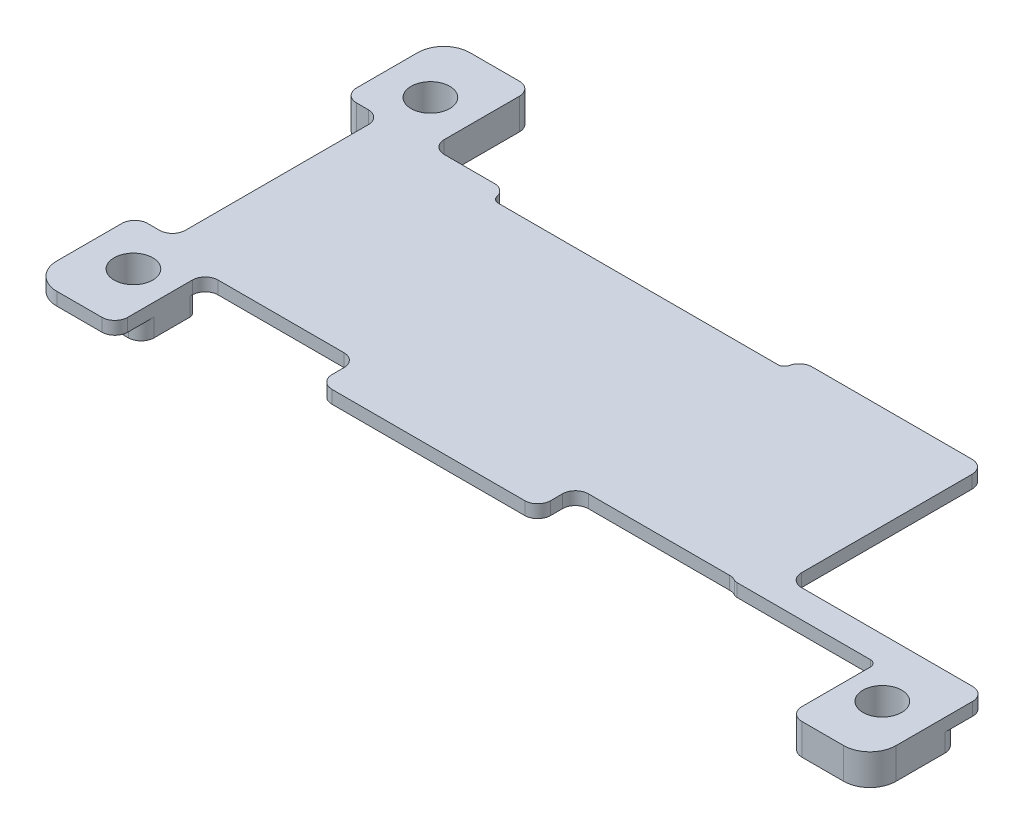
SolidWorks part; units mm, degrees
ref_plane "Front Plane" through (0, 0, 0) normal (0, 0, 1) x (1, 0, 0)
ref_plane "Top Plane" through (0, 0, 0) normal (0, 1, 0) x (1, 0, 0)
ref_plane "Right Plane" through (0, 0, 0) normal (1, 0, 0) x (0, 0, -1)
sketch "Sketch2" plane through (0, 0, 0) normal (0, 1, 0) x (1, 0, 0)
  line L4 (-32.5001, 13.9696) -> (-32.5001, -13.9696)
  line L5 (-30.4681, -16.0016) -> (30.4681, -16.0016)
  line L6 (32.5001, -13.9696) -> (32.5001, 13.9696)
  line L7 (30.4681, 16.0016) -> (-30.4681, 16.0016)
  line L8 (-32.5001, 13.9696) -> (-32.5001, -13.9696)
  line L9 (-30.4681, -16.0016) -> (30.4681, -16.0016)
  line L10 (32.5001, -13.9696) -> (32.5001, 13.9696)
  line L11 (30.4681, 16.0016) -> (-30.4681, 16.0016)
  circle A0 centre (28.9999, 11.4637) radius 1.5 construction
  circle A1 centre (28.9999, -11.5363) radius 1.5 construction
  circle A2 centre (-29.0002, -11.5363) radius 1.5 construction
  circle A3 centre (-29.0002, 11.4637) radius 1.5 construction
  arc A4 (-30.4681, 16.0016) -> (-32.5001, 13.9696) centre (-30.4681, 13.9696) ccw
  arc A5 (-32.5001, -13.9696) -> (-30.4681, -16.0016) centre (-30.4681, -13.9696) ccw
  arc A6 (30.4681, -16.0016) -> (32.5001, -13.9696) centre (30.4681, -13.9696) ccw
  arc A7 (32.5001, 13.9696) -> (30.4681, 16.0016) centre (30.4681, 13.9696) ccw
  arc A8 (-30.4681, 16.0016) -> (-32.5001, 13.9696) centre (-30.4681, 13.9696) ccw
  arc A9 (-32.5001, -13.9696) -> (-30.4681, -16.0016) centre (-30.4681, -13.9696) ccw
  arc A10 (30.4681, -16.0016) -> (32.5001, -13.9696) centre (30.4681, -13.9696) ccw
  arc A11 (32.5001, 13.9696) -> (30.4681, 16.0016) centre (30.4681, 13.9696) ccw
  circle A12 centre (28.9999, 11.4637) radius 1.5
  circle A13 centre (28.9999, -11.5363) radius 1.5
  circle A14 centre (-29.0002, -11.5363) radius 1.5
  circle A15 centre (-29.0002, 11.4637) radius 1.5
  dimension "D1" = 0
extrude "Boss-Extrude1" add sketch "Sketch2" along normal blind 1 from offset 1.4
sketch "Sketch4" plane through (0, 2.4, 0) normal (0, 1, 0) x (1, 0, 0)
  line L0 (30.4681, 16.0016) -> (-30.4681, 16.0016) construction
  line L1 (-25.6391, 16.0016) -> (25.6609, 16.0016)
  line L2 (-25.6391, 16.0016) -> (-25.6391, 8.1735)
  line L3 (-25.6391, 8.1735) -> (25.6609, 8.1735)
  line L4 (25.6609, 16.0016) -> (25.6609, 8.1735)
  line L5 (-25.3891, 13.7969) -> (-25.3891, 9.7969) construction
  line L7 (25.4109, 9.7969) -> (25.4109, 9.9469) construction
  line L8 (16.247, 7.1735) -> (3.847, 7.1735) construction
  dimension "D2" = 0.25
  dimension "D3" = 0.25
  dimension "D1" = 1
extrude "Cut-Extrude1" cut sketch "Sketch4" against normal through all
sketch "Sketch5" plane through (0, 2.4, 0) normal (0, 1, 0) x (1, 0, 0)
  line L1 (17.247, -7.0388) -> (32.5001, -7.0388)
  line L2 (17.247, -7.0388) -> (17.247, 16.0016)
  line L3 (17.247, 16.0016) -> (32.5001, 16.0016)
  line L4 (32.5001, -7.0388) -> (32.5001, 16.0016)
  line L6 (32.5001, 13.9696) -> (32.5001, -13.9696) construction
  line L7 (-30.4681, 16.0016) -> (30.4681, 16.0016) construction
  line L8 (16.247, -7.8265) -> (16.247, 7.1735) construction
  line L9 (29.9856, -6.8888) -> (19.7756, -6.8888) construction
  dimension "D1" = 1
  dimension "D2" = 0.15
extrude "Cut-Extrude2" cut sketch "Sketch5" against normal through all
sketch "Sketch6" plane through (0, 2.4, 0) normal (0, 1, 0) x (1, 0, 0)
  line L0 (-30.4681, -16.0016) -> (30.4681, -16.0016) construction
  line L1 (4.1693, -9.2016) -> (26.2388, -9.2016)
  line L2 (4.1693, -9.2016) -> (4.1693, -16.0016)
  line L3 (4.1693, -16.0016) -> (26.2388, -16.0016)
  line L4 (26.2388, -9.2016) -> (26.2388, -16.0016)
  line L5 (4.4193, -17.3016) -> (4.4193, -9.5016) construction
  line L6 (25.9888, -9.5016) -> (25.9888, -17.0016) construction
  line L7 (5.6693, -9.5016) -> (4.4193, -9.5016) construction
  line L8 (-14.475, -9.6016) -> (-14.475, -17.4016) construction
  line L9 (-25.975, -9.0016) -> (-14.225, -9.0016)
  line L10 (-25.975, -9.0016) -> (-25.975, -16.0016)
  line L11 (-25.975, -16.0016) -> (-14.225, -16.0016)
  line L12 (-14.225, -9.0016) -> (-14.225, -16.0016)
  line L13 (-25.725, -17.4016) -> (-25.725, -9.6016) construction
  line L15 (-10.0891, -9.0016) -> (-26.0891, -9.0016) construction
  dimension "D2" = 0.25
  dimension "D1" = 0.25
  dimension "D4" = 0.25
  dimension "D5" = 0.25
extrude "Cut-Extrude3" cut sketch "Sketch6" against normal through all
sketch "Sketch7" plane through (0, 2.4, 0) normal (0, 1, 0) x (1, 0, 0)
  line L0 (-30.4681, -16.0016) -> (-25.975, -16.0016) construction
  line L2 (2.6974, -11.9253) -> (2.6974, -9.0016)
  line L4 (15.247, -16.0016) -> (15.247, -9.0016)
  line L5 (16.247, -7.8265) -> (16.247, 7.1735) construction
  line L7 (1.6974, -10.9253) -> (1.6974, 4.0747) construction
  line L8 (-13.3026, -10.9253) -> (1.6974, -10.9253) construction
  line L9 (-14.225, -16.0016) -> (15.247, -16.0016)
  line L10 (-14.225, -16.0016) -> (-14.225, -11.9253)
  line L11 (-14.225, -11.9253) -> (2.6974, -11.9253)
  line L13 (-32.5001, 13.9696) -> (-32.5001, -13.9696) construction
  line L14 (-32.5001, 8.2393) -> (-29.5778, 8.2393)
  line L15 (-32.5001, 8.2393) -> (-32.5001, -7.9342)
  line L16 (-32.5001, -7.9342) -> (-29.5778, -7.9342)
  line L17 (-29.5778, 8.2393) -> (-29.5778, -7.9342)
  line L18 (-28.5778, 3.8025) -> (-28.5778, -4.1975) construction
  line L19 (-31.8265, 8.1393) -> (-31.2801, 8.1393) construction
  line L20 (-29.6497, -7.8342) -> (-28.7533, -7.8342) construction
  line L21 (2.6974, -9.0016) -> (15.247, -9.0016)
  line L23 (-25.6391, 8.1735) -> (17.247, 8.1735) construction
  line L24 (-19.7521, 8.1735) -> (2.847, 8.1735)
  line L25 (-19.7521, 8.1735) -> (-19.7521, 6.9984)
  line L26 (-19.7521, 6.9984) -> (2.847, 6.9984)
  line L27 (2.847, 8.1735) -> (2.847, 6.9984)
  line L28 (-9.9891, 6.9984) -> (6.0109, 6.9984) construction
  line L29 (3.847, 7.1735) -> (3.847, -7.8265) construction
  line L30 (-20.7521, 4.5096) -> (-20.7521, 7.4306) construction
  dimension "D1" = 1
  dimension "D3" = 1
  dimension "D4" = 1
  dimension "D5" = 1
  dimension "D6" = 0.1
  dimension "D7" = 0.1
  dimension "D2" = 1
  dimension "D8" = 1
extrude "Cut-Extrude4" cut sketch "Sketch7" against normal through all
fillet "Fillet8" radius 1 19 edges at (15.247, 1.9, 9.0016) (-29.5778, 1.9, 7.9342) (-32.5001, 1.9, 7.9342) (-25.975, 1.9, 16.0016) (-25.975, 1.9, 9.0016) (-14.225, 1.9, 9.0016) (-14.225, 1.9, 11.9253) (2.6974, 1.9, 11.9253) (2.6974, 1.9, 9.0016) (26.2388, 1.9, 16.0016) (17.247, 1.9, 7.0388) (17.247, 1.9, -8.1735) (2.847, 1.9, -8.1735) (-19.7521, 1.9, -8.1735) (-25.6391, 1.9, -8.1735) (-25.6391, 1.9, -16.0016) (-32.5001, 1.9, -8.2393) (-29.5778, 1.9, -8.2393) (32.5001, 1.9, 7.0388)
fillet "Fillet10" radius 0.5 1 edges at (26.2388, 1.9, 9.2016)
sketch "Sketch9" plane through (0, 1.4, 0) normal (0, -1, 0) x (1, 0, 0)
  line L4 (16.247, -7.1735) -> (16.247, 7.8265)
  line L5 (3.847, -7.1735) -> (16.247, -7.1735)
  line L6 (3.847, 7.8265) -> (3.847, -7.1735)
  line L7 (16.247, 7.8265) -> (3.847, 7.8265)
  line L8 (16.247, -7.1735) -> (16.247, 7.8265)
  line L9 (3.847, -7.1735) -> (16.247, -7.1735)
  line L10 (3.847, 7.8265) -> (3.847, -7.1735)
  line L11 (16.247, 7.8265) -> (3.847, 7.8265)
  line L12 (1.6974, -4.0747) -> (1.6974, 10.9253)
  line L13 (-13.3026, -4.0747) -> (1.6974, -4.0747)
  line L14 (-13.3026, 10.9253) -> (-13.3026, -4.0747)
  line L15 (1.6974, 10.9253) -> (-13.3026, 10.9253)
  line L16 (1.6974, -4.0747) -> (1.6974, 10.9253)
  line L17 (-13.3026, -4.0747) -> (1.6974, -4.0747)
  line L18 (-13.3026, 10.9253) -> (-13.3026, -4.0747)
  line L19 (1.6974, 10.9253) -> (-13.3026, 10.9253)
  dimension "D1" = 0
  dimension "D2" = 0
extrude "Boss-Extrude2" add sketch "Sketch9" along normal offset from surface (0.35 mm away) 0.05
fillet "Fillet3" radius 0.5 8 edges at (3.847, 1.225, 7.8265) (3.847, 1.225, -7.1735) (16.247, 1.225, -7.1735) (16.247, 1.225, 7.8265) (-13.3026, 1.225, 10.9253) (-13.3026, 1.225, -4.0747) (1.6974, 1.225, -4.0747) (1.6974, 1.225, 10.9253)
sketch "Sketch10" plane through (0, 2.4, 0) normal (0, 1, 0) x (1, 0, 0)
  line L0 (-30.5778, 8.2393) -> (-25.6391, 8.2393)
  line L1 (-25.6391, 8.2393) -> (-25.6391, 9.1735)
  line L2 (-25.6391, 15.0016) -> (-25.6391, 9.1735) construction
  line L3 (-30.5778, 8.2393) -> (-31.5001, 8.2393) construction
  line L4 (-32.5001, 13.9696) -> (-32.5001, 9.2393) construction
  line L5 (-26.6391, 16.0016) -> (-30.4681, 16.0016) construction
  line L6 (-30.5778, 8.2393) -> (-31.5001, 8.2393)
  line L7 (-32.5001, 13.9696) -> (-32.5001, 9.2393)
  line L8 (-26.6391, 16.0016) -> (-30.4681, 16.0016)
  line L9 (-25.6391, 15.0016) -> (-25.6391, 9.1735)
  line L10 (-25.975, -10.0016) -> (-25.975, -15.0016) construction
  line L12 (-32.5001, -8.9342) -> (-32.5001, -13.9696) construction
  line L13 (-31.5001, -7.9342) -> (-30.5778, -7.9342) construction
  line L14 (-25.975, -10.0016) -> (-25.975, -13.9587)
  line L16 (-32.5001, -8.9342) -> (-32.5001, -13.9587)
  line L17 (-31.5001, -7.9342) -> (-30.5778, -7.9342)
  line L18 (26.2388, -9.7016) -> (26.2388, -9.1856)
  line L19 (26.2388, -9.1856) -> (32.5001, -9.1856)
  line L20 (32.5001, -13.9696) -> (32.5001, -8.0388) construction
  line L21 (32.5001, -13.9696) -> (32.5001, -9.1856)
  line L22 (26.2388, -15.0016) -> (26.2388, -9.7016) construction
  line L23 (27.2388, -16.0016) -> (30.4681, -16.0016) construction
  line L24 (26.2388, -15.0016) -> (26.2388, -9.7016)
  line L25 (27.2388, -16.0016) -> (30.4681, -16.0016)
  line L26 (-32.5001, -13.9587) -> (-25.975, -13.9587)
  circle A0 centre (28.9999, -11.5363) radius 1.5 construction
  arc A1 (-32.5001, 9.2393) -> (-31.5001, 8.2393) centre (-31.5001, 9.2393) ccw construction
  arc A2 (-30.4681, 16.0016) -> (-32.5001, 13.9696) centre (-30.4681, 13.9696) ccw construction
  arc A3 (-25.6391, 15.0016) -> (-26.6391, 16.0016) centre (-26.6391, 15.0016) ccw construction
  arc A4 (-32.5001, 9.2393) -> (-31.5001, 8.2393) centre (-31.5001, 9.2393) ccw
  arc A5 (-30.4681, 16.0016) -> (-32.5001, 13.9696) centre (-30.4681, 13.9696) ccw
  arc A6 (-25.6391, 15.0016) -> (-26.6391, 16.0016) centre (-26.6391, 15.0016) ccw
  circle A7 centre (-29.0002, 11.4637) radius 1.5 construction
  circle A8 centre (-29.0002, 11.4637) radius 1.5
  arc A9 (-30.5778, -7.9342) -> (-25.975, -10.0016) centre (-30.5778, -14.0917) cw
  arc A10 (26.2388, -15.0016) -> (27.2388, -16.0016) centre (27.2388, -15.0016) ccw construction
  arc A13 (-31.5001, -7.9342) -> (-32.5001, -8.9342) centre (-31.5001, -8.9342) ccw construction
  arc A16 (-31.5001, -7.9342) -> (-32.5001, -8.9342) centre (-31.5001, -8.9342) ccw
  circle A17 centre (-29.0002, -11.5363) radius 1.5 construction
  circle A18 centre (-29.0002, -11.5363) radius 1.5
  arc A19 (30.4681, -16.0016) -> (32.5001, -13.9696) centre (30.4681, -13.9696) ccw construction
  circle A20 centre (28.9999, -11.5363) radius 1.5
  arc A21 (26.2388, -15.0016) -> (27.2388, -16.0016) centre (27.2388, -15.0016) ccw
  arc A22 (30.4681, -16.0016) -> (32.5001, -13.9696) centre (30.4681, -13.9696) ccw
  dimension "D1" = 0.25
extrude "Boss-Extrude3" add sketch "Sketch10" against normal up to surface (2.4 mm away)
fillet "Fillet6" radius 0.5 4 edges at (15.247, 1.9, 9.2016) (2.847, 1.9, -6.9984) (-19.7521, 1.9, -6.9984) (-25.6391, 0.7, -8.2393)
fillet "Fillet11" radius 1 3 edges at (32.5001, 0.7, 9.1856) (-25.975, 0.7, 13.9587) (-32.5001, 0.7, 13.9587)
fillet "Fillet13" radius 0.5 2 edges at (26.2388, 0.7, 9.1856) (-25.975, 0.7, 10.0016)
equation "\"K1\"= 0.3"
equation "\"K2\"=0.25"
equation "\"K3\"=0.2"
equation "\"K4\"= 0.15"
equation "\"K5\"= 0.1"
equation "\"K6\"= 0.05"
equation "\"D2@Sketch4\"=\"K2\""
equation "\"D3@Sketch4\"=\"K2\""
equation "\"expand\"= 1"
equation "\"D1@Sketch4\"=\"expand\""
equation "\"D1@Sketch5\"=\"expand\""
equation "\"D2@Sketch5\"=\"K4\""
equation "\"D1@Sketch6\"=\"K2\""
equation "\"D2@Sketch6\"=\"K2\""
equation "\"D3@Sketch6\"=\"K1\""
equation "\"D1@Sketch7\"=\"expand\""
equation "\"D3@Sketch7\"=\"expand\""
equation "\"D4@Sketch6\"=\"K2\""
equation "\"D5@Sketch6\"=\"K2\""
equation "\"D4@Sketch7\"=\"expand\""
equation "\"D5@Sketch7\"=\"expand\""
equation "\"D6@Sketch7\"=\"K5\""
equation "\"D7@Sketch7\"=\"K5\""
equation "\"D2@Sketch7\"=\"expand\""
equation "\"D8@Sketch7\"=\"expand\""
equation "\"D1@Sketch10\"=\"K2\""
equation "\"D2@Sketch10\"=\"K1\""
